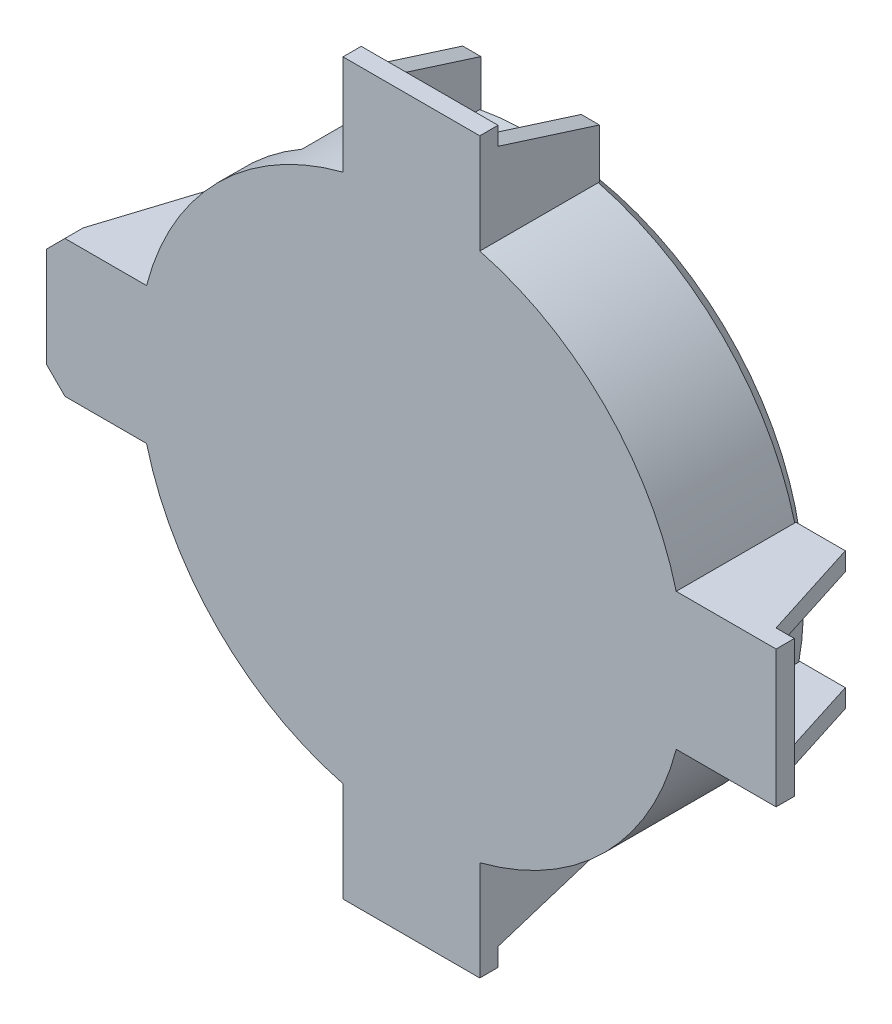
SolidWorks part; units mm, degrees
ref_plane "Front Plane" through (0, 0, 0) normal (1, 0, 0) x (0, 1, 0)
ref_plane "Top Plane" through (0, 0, 0) normal (0, 0, 1) x (0, 1, 0)
ref_plane "Right Plane" through (0, 0, 0) normal (0, 1, 0) x (-1, 0, 0)
sketch "Sketch1" plane through (0, 0, 0) normal (0, 0, 1) x (0, 1, 0)
  circle A0 centre (0, 0) radius 150
  dimension "D1" = 300
extrude "Boss-Extrude1" add sketch "Sketch1" along normal blind 75
chamfer "Chamfer1" distance 10 angle 45 1 edges at (150, 0, 0)
sketch "Sketch2" plane through (0, 0, 75) normal (0, 0, 1) x (1, 0, 0)
  line L1 (-200, -37.5) -> (-145.2369, -37.5)
  line L2 (-200, -37.5) -> (-200, 37.5)
  line L3 (-200, 37.5) -> (-145.2369, 37.5)
  circle A0 centre (0, 0) radius 150 construction
  circle A1 centre (0, 0) radius 150
  point P0 (-150, 0)
  circle M6 centre (0, 0) radius 150
extrude "Boss-Extrude2" add sketch "Sketch2" against normal blind 10 contours L3 L2 L1 M6 region at (-174.1918, 0, 75)
chamfer "Chamfer2" distance 10 angle 45 2 edges at (-200, -37.5, 70) (-200, 37.5, 70)
sketch "Sketch3" plane through (0, 37.5, 0) normal (0, 1, 0) x (-1, 0, 0)
  line L0 (145.2369, 65) -> (145.2369, 9.354)
  line L1 (145.2369, 9.354) -> (172.32, 9.354)
  line L2 (172.32, 9.354) -> (190, 65)
  line L3 (190, 65) -> (145.2369, 65)
  line L4 (190, 65) -> (190, 75) construction
  line L5 (190, 65) -> (145.2369, 65) construction
  dimension "D1" = 17.68
  dimension "D2" = 55.646
extrude "Boss-Extrude3" add sketch "Sketch3" against normal blind 10
sketch "Sketch4" plane through (0, 0, 65) normal (0, 0, -1) x (1, 0, 0)
  line L0 (-190, 37.5) -> (-190, -59.6832) construction
  line L2 (-190, -9.4096) -> (-195.1962, -12.4096)
  line L3 (-195.1962, -12.4096) -> (-195.1962, -18.4096)
  line L4 (-195.1962, -18.4096) -> (-190, -21.4096)
  line L5 (-190, -21.4096) -> (-184.8038, -18.4096)
  line L6 (-184.8038, -18.4096) -> (-184.8038, -12.4096)
  line L7 (-184.8038, -12.4096) -> (-190, -9.4096)
  circle A0 centre (-190, -15.4096) radius 5.1962 construction
  dimension "D1" = 6
extrude "Boss-Extrude4" add sketch "Sketch4" along normal blind 3.5
mirror "Mirror1" about plane through (0, 0, 0) normal (0, 1, 0) of "Boss-Extrude3", "Boss-Extrude4"
pattern_circular "CirPattern1" count 4 over 360 about axis through (0, 0, 75) along (0, 0, 1) of "Boss-Extrude2", "Boss-Extrude3", "Boss-Extrude4", "Mirror1"
sketch "Sketch5" plane through (0, 0, 0) normal (0, 0, -1) x (1, 0, 0)
  line L2 (-112.5833, -65) -> (-129.9038, -75)
  line L3 (-65, -112.5833) -> (-75, -129.9038)
  arc A0 (-112.5833, -65) -> (-65, -112.5833) centre (0, 0) ccw
  arc A1 (-145.2369, -37.5) -> (-37.5, -145.2369) centre (0, 0) ccw construction
  arc A2 (-129.9038, -75) -> (-75, -129.9038) centre (0, 0) ccw
extrude "Cut-Extrude1" cut sketch "Sketch5" against normal blind 60
sketch "Sketch6" plane through (0, 0, 0) normal (0, 0, -1) x (1, 0, 0)
  circle A0 centre (0, 0) radius 110
  dimension "D1" = 220
extrude "Boss-Extrude5" add sketch "Sketch6" along normal blind 10
chamfer "Chamfer3" distance 15 angle 45 1 edges at (-110, 0, -10)
sketch "Sketch7" plane through (0, 0, -10) normal (0, 0, -1) x (1, 0, 0)
  circle A0 centre (0, 0) radius 15
  dimension "D1" = 30
extrude "Boss-Extrude6" add sketch "Sketch7" along normal blind 20
ref_point "Point1"
